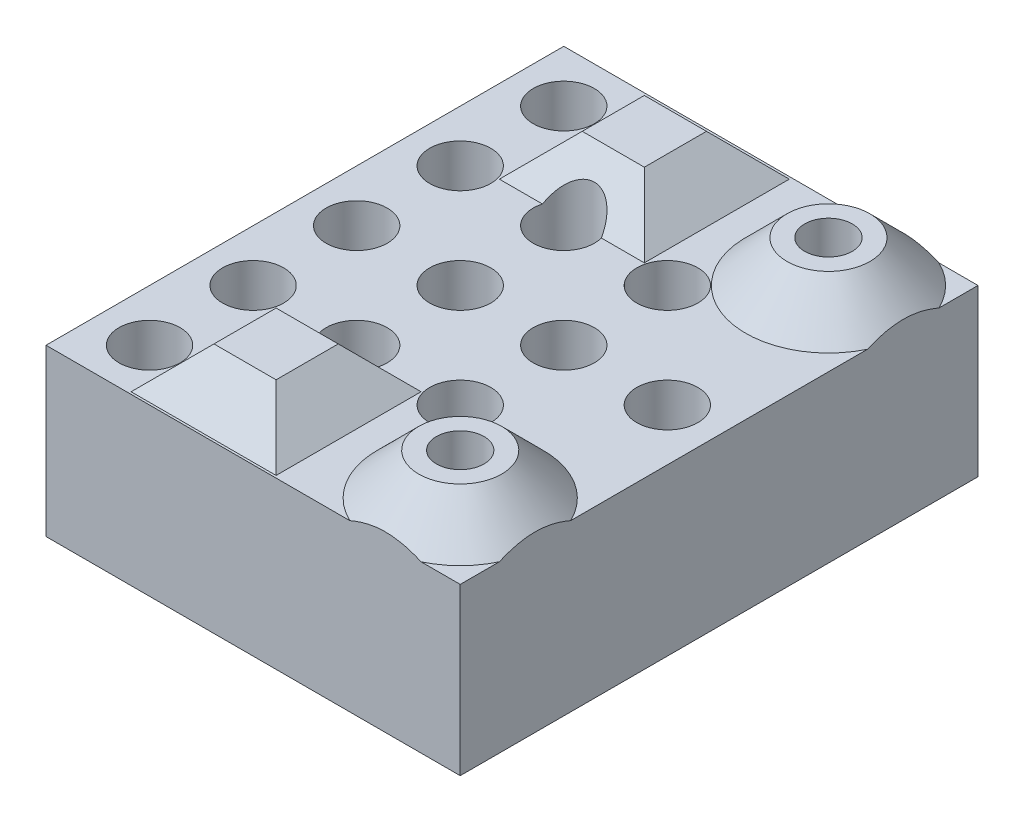
SolidWorks part; units mm, degrees
ref_plane "Front Plane" through (0, 0, 0) normal (0, 0, 1) x (1, 0, 0)
ref_plane "Top Plane" through (0, 0, 0) normal (0, 1, 0) x (1, 0, 0)
ref_plane "Right Plane" through (0, 0, 0) normal (1, 0, 0) x (0, 0, -1)
sketch "Sketch1" plane through (0, 0, 0) normal (0, 1, 0) x (1, 0, 0)
  line L1 (-12.5, 12.5) -> (12.5, 12.5)
  line L2 (-12.5, 12.5) -> (-12.5, -12.5)
  line L3 (-12.5, -12.5) -> (12.5, -12.5)
  line L4 (12.5, 12.5) -> (12.5, -12.5)
  line L5 (-12.5, 12.5) -> (12.5, -12.5) construction
  line L6 (-12.5, -12.5) -> (12.5, 12.5) construction
  point P0 (0, 0)
  dimension "D1" = 25
  dimension "D2" = 25
extrude "Boss-Extrude1" add sketch "Sketch1" along normal blind 8
sketch "Sketch2" plane through (0, 8, 0) normal (0, 1, 0) x (1, 0, 0)
  line L1 (8.89, -8.89) -> (-8.89, -8.89) construction
  line L2 (8.89, -8.89) -> (8.89, 8.89) construction
  line L3 (8.89, 8.89) -> (-8.89, 8.89) construction
  line L4 (-8.89, -8.89) -> (-8.89, 8.89) construction
  line L5 (8.89, -8.89) -> (-8.89, 8.89) construction
  line L6 (8.89, 8.89) -> (-8.89, -8.89) construction
  circle A0 centre (-8.89, 8.89) radius 0.95 construction
  circle A1 centre (-8.89, -8.89) radius 0.95 construction
  circle A2 centre (8.89, -8.89) radius 0.95
  circle A3 centre (8.89, 8.89) radius 0.95
  point P0 (0, 0)
  dimension "D1" = 1.9
  dimension "D2" = 17.78
  dimension "D3" = 17.78
extrude "Cut-Extrude1" cut sketch "Sketch2" against normal through all
sketch "Sketch3" plane through (0, 8, 0) normal (0, 1, 0) x (1, 0, 0)
  circle A2 centre (8.89, 8.89) radius 2
  circle A3 centre (8.89, -8.89) radius 2
  circle A4 centre (8.89, -8.89) radius 0.95 construction
  circle A5 centre (8.89, 8.89) radius 0.95 construction
  circle A8 centre (8.89, -8.89) radius 0.95
  circle A9 centre (8.89, 8.89) radius 0.95
  dimension "D1" = 4
extrude "Boss-Extrude2" add sketch "Sketch3" along normal blind 2
sketch "Sketch6" plane through (0, 8, 0) normal (0, 1, 0) x (1, 0, 0)
  line L1 (-1.5, 10.39) -> (1.5, 10.39)
  line L2 (-1.5, 10.39) -> (-1.5, 7.39)
  line L3 (-1.5, 7.39) -> (1.5, 7.39)
  line L4 (1.5, 10.39) -> (1.5, 7.39)
  line L5 (-1.5, 10.39) -> (1.5, 7.39) construction
  line L6 (-1.5, 7.39) -> (1.5, 10.39) construction
  line L7 (-1.5, -7.39) -> (1.5, -7.39)
  line L8 (-1.5, -7.39) -> (-1.5, -10.39)
  line L9 (-1.5, -10.39) -> (1.5, -10.39)
  line L10 (1.5, -7.39) -> (1.5, -10.39)
  line L11 (-1.5, -7.39) -> (1.5, -10.39) construction
  line L12 (-1.5, -10.39) -> (1.5, -7.39) construction
  point P0 (0, 8.89)
  point P5 (0, -8.89)
  point P10 (8.89, -8.89)
  point P14 (8.89, 8.89)
  dimension "D1" = 3
extrude "Boss-Extrude3" add sketch "Sketch6" along normal up to surface (2 mm away) up to face at (8.89, 10, -6.89)
chamfer "Chamfer1" distance 2 angle 45 10 edges at (8.89, 8, -6.89) (8.89, 8, 10.89) (0, 8, 7.39) (1.5, 8, 8.89) (0, 8, 10.39) (-1.5, 8, 8.89) (1.5, 8, -8.89) (0, 8, -10.39) (-1.5, 8, -8.89) (0, 8, -7.39)
sketch "Sketch4" plane through (0, 0, 0) normal (0, -1, 0) x (1, 0, 0)
  circle A0 centre (-10, 0) radius 1.475
  dimension "D1" = 2.95
  dimension "D2" = 10
extrude "Cut-Extrude2" cut sketch "Sketch4" against normal through all
pattern_linear "LPattern1" count 5 spacing 5 along (1, 0, 0) count 3 spacing 5 along (0, 0, 1) skipping (2, 2), (3, 2), (4, 1), (4, 2) of "Cut-Extrude2"
mirror "Mirror1" about plane through (0, 0, 0) normal (0, 0, 1) of "LPattern1"
sketch "Sketch5" plane through (0, 10, 0) normal (0, 1, 0) x (1, 0, 0)
  circle A2 centre (8.89, 8.89) radius 1.15
  circle A3 centre (8.89, -8.89) radius 1.15
  dimension "D1" = 2.3
extrude "Cut-Extrude3" cut sketch "Sketch5" against normal blind 2
sketch "Sketch7" plane through (0, 8, 0) normal (0, 1, 0) x (1, 0, 0)
  line L0 (-12.5, -12.5) -> (7.1672, -12.5) construction
  line L1 (-12.5, 12.5) -> (-7.5, 12.5)
  line L2 (-12.5, 12.5) -> (-12.5, -12.5)
  line L3 (-12.5, -12.5) -> (-7.5, -12.5)
  line L4 (-7.5, 12.5) -> (-7.5, -12.5)
  dimension "D1" = 5
extrude "Cut-Extrude4" cut sketch "Sketch7" against normal through all
